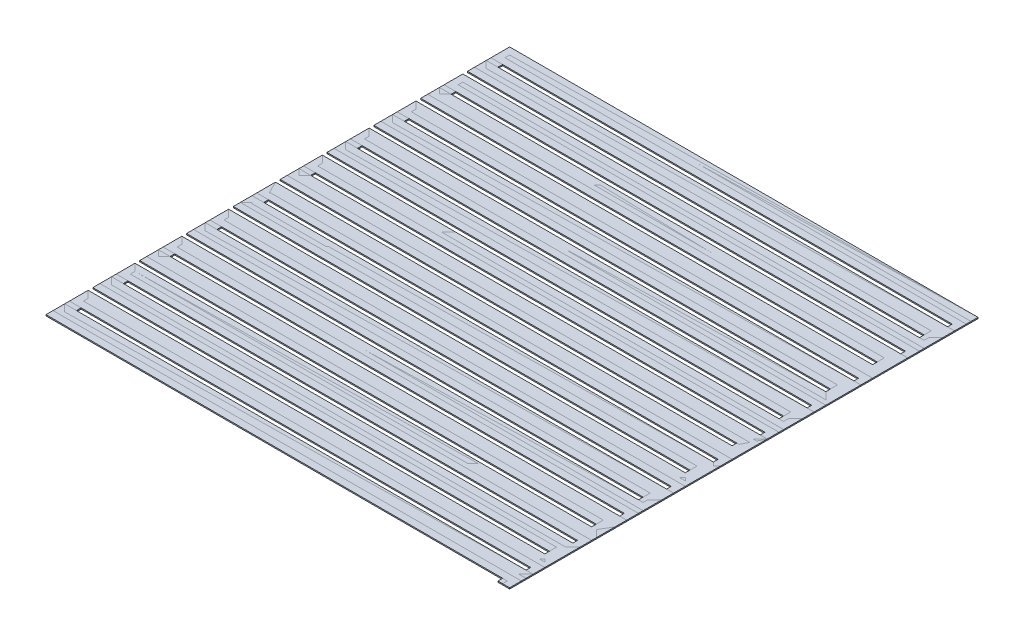
SolidWorks part; units mm, degrees
ref_plane "Front Plane" through (0, 0, 0) normal (0, 0, 1) x (1, 0, 0)
ref_plane "Top Plane" through (0, 0, 0) normal (0, 1, 0) x (1, 0, 0)
ref_plane "Right Plane" through (0, 0, 0) normal (1, 0, 0) x (0, 0, -1)
sketch "Base Guidlines" plane through (0, 0, 0) normal (0, 1, 0) x (1, 0, 0)
  line L0 (-4.5961, 9.2) -> (-4.5961, 8.5)
  line L1 (-10, -10) -> (10, -10)
  line L2 (-10, -10) -> (-10, 10)
  line L3 (-10, 10) -> (10, 10)
  line L4 (10, -10) -> (10, 10)
  line L5 (-10, -10) -> (10, 10) construction
  line L6 (-10, 10) -> (10, -10) construction
  line L7 (-10, 10) -> (10, 10)
  line L8 (-10, 10) -> (-10, 9.2)
  line L9 (-10, 9.2) -> (10, 9.2)
  line L10 (10, 10) -> (10, 9.2)
  line L11 (-4.5961, -9.2) -> (-4.5961, -8.5)
  line L12 (-10, -10) -> (10, -10)
  line L13 (-10, -10) -> (-10, -9.2)
  line L14 (-10, -9.2) -> (10, -9.2)
  line L15 (10, -10) -> (10, -9.2)
  line L17 (-10, -9.2) -> (10, -9.2)
  line L18 (-10, -9.2) -> (-10, -8.5)
  line L19 (-10, -8.5) -> (10, -8.5)
  line L20 (10, -9.2) -> (10, -8.5)
  line L21 (-10, 9.2) -> (10, 9.2)
  line L22 (-10, 9.2) -> (-10, 8.5)
  line L23 (-10, 8.5) -> (10, 8.5)
  line L24 (10, 9.2) -> (10, 8.5)
  point P0 (0, 0)
  dimension "D1" = 20
  dimension "D2" = 20
  dimension "D3" = 0.7
  dimension "D4" = 0.7
sketch "Mirror axis x" plane through (0, 0, 0) normal (0, 1, 0) x (1, 0, 0)
  line L0 (-10, 0) -> (10, 0)
  line L1 (-10, -10) -> (-10, 10) construction
  line L2 (10, -10) -> (10, 10) construction
sketch "TopBlock" plane through (0, 0, 0) normal (0, 1, 0) x (1, 0, 0)
  line L0 (-10, 10) -> (10, -10) construction
  line L1 (-10, 10) -> (-9.7, 10)
  line L2 (-10, 10) -> (-10, 9.7)
  line L3 (10, 9.2) -> (10, 9.5)
  line L4 (-9.7, 10) -> (10, 10)
  line L5 (-9.7, 9.7) -> (-9.7, 9.5)
  line L6 (-10, 9.2) -> (-9.7, 9.2)
  line L7 (-10, 9.2) -> (-10, 9.5)
  line L8 (-9.7, 9.5) -> (9.7, 9.5)
  line L10 (-10, 9.7) -> (-10, 9.5)
  line L11 (-9.7, 9.7) -> (10, 9.7)
  line L12 (10, 9.7) -> (10, 10)
  line L13 (10, -10) -> (10, 10) construction
  line L14 (10, 9.2) -> (9.7, 9.2)
  line L15 (10, 9.5) -> (9.7, 9.5)
  line L24 (9.7, 9.2) -> (-9.7, 9.2)
  dimension "D1" = 0.3
  dimension "D2" = 0.3
extrude "Extruded object" add sketch "TopBlock" along normal blind 0.05
sketch "Mirror axis y" plane through (0, 0, 0) normal (0, 1, 0) x (1, 0, 0)
  line L0 (0, 10) -> (0, -10)
  line L3 (10, 10) -> (-10, 10) construction
  dimension "D1" = 20
sketch "GapandInbetween" plane through (0, 0, 0) normal (0, 1, 0) x (1, 0, 0)
  line L0 (10, 9.2) -> (10, 9)
  line L1 (10, -10) -> (10, 10) construction
  line L2 (10, 9) -> (10, 8.7)
  line L3 (-9.7, 8.5) -> (-9.7, 8.7)
  line L4 (9.7, 9) -> (9.7, 9.2)
  line L5 (-10, 9.2) -> (10, 9.2) construction
  line L6 (9.7, 9.2) -> (10, 9.2)
  line L7 (10, 8.7) -> (-9.7, 8.7)
  line L8 (-10, -10) -> (-10, 10) construction
  line L9 (9.7, 9) -> (-10, 9)
  line L10 (-10, 9) -> (-10, 8.7)
  line L11 (-10, 8.7) -> (-10, 8.5)
  line L12 (-9.7, 8.5) -> (10, 8.5)
  line L13 (-10, 8.5) -> (10, 8.5) construction
  line L14 (-10, 8.5) -> (-10, 8.2)
  line L15 (-10, 8.2) -> (9.7, 8.2)
  line L16 (9.7, 8.2) -> (10, 8.2)
  line L17 (10, 8.2) -> (10, 8.5)
  dimension "D1" = 0.2
  dimension "D2" = 0.3
  dimension "D3" = 0.3
  dimension "D4" = 0.3
  dimension "D5" = 0.3
  dimension "D6" = 19.7
extrude "Boss-Extrude2" add sketch "GapandInbetween" along normal blind 0.05
pattern_linear "LPattern1" count 19 spacing 1 along (0, 0, 1) of "Boss-Extrude2"
sketch "Sketch1" plane through (0, 0, 0) normal (0, 1, 0) x (1, 0, 0)
  line L1 (10, -9.8) -> (10, -10)
  line L2 (9.7, -9.8) -> (9.7, -10)
  line L3 (9.7, -10) -> (10, -10)
  line L4 (10, -9.8) -> (9.7, -9.8)
  line L5 (-10, -9.8) -> (10, -9.8) construction
  dimension "D1" = 0.2
extrude "Boss-Extrude3" add sketch "Sketch1" along normal blind 0.05
sketch "Sketch2" plane through (0, 0, 0) normal (0, 1, 0) x (1, 0, 0)
  line L1 (-10, 10) -> (10, 10)
  line L2 (-10, 10) -> (-10, -10)
  line L3 (-10, -10) -> (10, -10)
  line L4 (10, 10) -> (10, -10)
  dimension "D1" = 20
extrude "Boss-Extrude4" add sketch "Sketch2" along normal blind 0.05 separate body
sketch "Sketch3" plane through (0, 0, 0) normal (0, 1, 0) x (1, 0, 0)
  line L0 (10, -10) -> (10, 10) construction
  line L1 (10, 9.5) -> (-9.5, 9.5)
  line L2 (10, 9.5) -> (10, 9)
  line L3 (10, 9) -> (-9.5, 9)
  line L4 (-9.5, 9.5) -> (-9.5, 9)
  line L5 (10, 10) -> (-10, 10) construction
  line L6 (-10, 10) -> (-10, -10) construction
  dimension "D1" = 0.5
  dimension "D2" = 0.5
  dimension "D3" = 0.5
sketch "Sketch4" plane through (0, 0, 0) normal (0, 1, 0) x (1, 0, 0)
  line L0 (-10, 10) -> (-10, -10) construction
  line L1 (-10, 8.5) -> (9.5, 8.5)
  line L2 (-10, 8.5) -> (-10, 8)
  line L3 (-10, 8) -> (9.5, 8)
  line L4 (9.5, 8.5) -> (9.5, 8)
  line L5 (10, 9) -> (-9.5, 9) construction
  line L6 (10, -10) -> (10, 10) construction
  dimension "D1" = 0.5
  dimension "D2" = 0.5
  dimension "D3" = 0.5
extrude "Cut-Extrude3" cut sketch "Sketch3" along normal blind 0.05
extrude "Cut-Extrude5" cut sketch "Sketch4" along normal blind 0.05
pattern_linear "LPattern2" count 10 spacing 2 along (0, 0, 1) of "Cut-Extrude3"
pattern_linear "LPattern3" count 10 spacing 2 along (0, 0, 1) of "Cut-Extrude5"
sketch "Sketch5" plane through (0, 0, 0) normal (0, -1, 0) x (1, 0, 0)
  line L0 (10, 0) -> (-10, 0) construction
  line L1 (10, -10) -> (-10, -10) construction
  line L2 (10, -10) -> (10, 10) construction
  line L3 (10, 10) -> (-10, 10) construction
  line L4 (-10, -10) -> (-10, 10) construction
  line L5 (0, -10) -> (0, 10) construction
  line L6 (10, -10) -> (0, 0) construction
  line L7 (0, 0) -> (-10, -10) construction
  line L8 (0, 0) -> (-10, 10) construction
  line L9 (0, 0) -> (10, 10) construction
  point P15 (5, -5)
  point P16 (-5, -5)
  point P17 (-5, 5)
  point P18 (5, 5)
sketch "Sketch6" plane through (0, 0, 0) normal (1, 0, 0) x (0, 0, -1)
  line L0 (0, -0.8164) -> (0, 2.1169) construction
sketch "Sketch7" plane through (0, 0, 0) normal (0, -1, 0) x (1, 0, 0)
  line L1 (10, 10) -> (-10, 10)
  line L2 (10, 10) -> (10, -10)
  line L3 (10, -10) -> (-10, -10)
  line L4 (-10, 10) -> (-10, -10)
